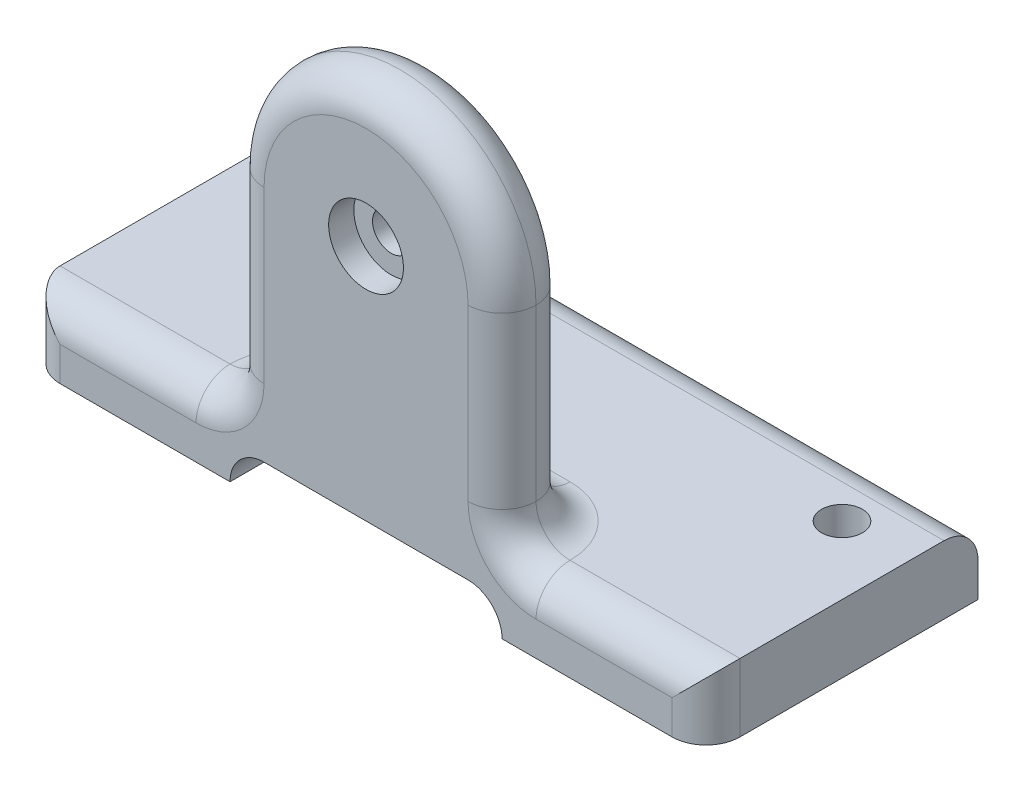
SolidWorks part; units mm, degrees
ref_plane "Plano frontal" through (0, 0, 0) normal (0, 0, 1) x (1, 0, 0)
ref_plane "Plano superior" through (0, 0, 0) normal (0, 1, 0) x (1, 0, 0)
ref_plane "Plano direito" through (0, 0, 0) normal (1, 0, 0) x (0, 0, -1)
sketch "Esboço1" plane through (0, 0, 0) normal (0, 1, 0) x (1, 0, 0)
  line L1 (-50, 20) -> (50, 20)
  line L2 (-50, 20) -> (-50, -20)
  line L3 (-50, -20) -> (50, -20)
  line L4 (50, 20) -> (50, -20)
  line L5 (-50, 20) -> (50, -20) construction
  line L6 (-50, -20) -> (50, 20) construction
  point P0 (0, 0)
  dimension "D1" = 100
  dimension "D2" = 40
extrude "Ressalto-extrusão1" add sketch "Esboço1" along normal blind 10
sketch "Esboço2" plane through (0, 0, 20) normal (0, 0, 1) x (1, 0, 0)
  line L0 (-20, 0) -> (-20, 40)
  line L1 (-50, 0) -> (50, 0) construction
  line L2 (20, 40) -> (20, 0)
  line L3 (20, 0) -> (-20, 0)
  arc A0 (-20, 40) -> (20, 40) centre (0, 40) cw
  dimension "D1" = 20
  dimension "D2" = 40
  dimension "D3" = 50
extrude "Ressalto-extrusão2" add sketch "Esboço2" against normal blind 10
sketch "Esboço3" plane through (0, 10, 0) normal (0, 1, 0) x (1, 0, 0)
  line L0 (50, 20) -> (-50, 20) construction
  line L1 (-50, 20) -> (-50, -20) construction
  line L2 (50, -20) -> (50, 20) construction
  circle A0 centre (-40, 10) radius 3
  circle A1 centre (40, 10) radius 3
  dimension "D4" = 6
  dimension "D5" = 6
  dimension "D1" = 10
  dimension "D2" = 10
  dimension "D3" = 10
extrude "Corte-extrusão1" cut sketch "Esboço3" against normal through all
sketch "Esboço4" plane through (0, 0, 20) normal (0, 0, 1) x (1, 0, 0)
  arc A0 (20, 40) -> (-20, 40) centre (0, 40) ccw construction
  point P0 (0, 40)
hole_wizard "Rebaixo para parafuso com cabeça panela de M51" positions "3DSketch1" profile "Esboço5" counterbore size "M5" standard "ISO" end condition up to next
sketch3d "3DSketch1"
  point P0 (0, 40, 20)
sketch "Esboço5" plane through (0, 40, 20) normal (1, 0, 0) x (0, -1, 0)
  line L0 (0, 0) -> (0, 10)
  line L1 (0, 10) -> (2.75, 10)
  line L3 (2.75, 10) -> (2.75, 3.7)
  line L4 (2.75, 3.7) -> (5.5, 3.7)
  line L5 (5.5, 3.7) -> (5.5, 0)
  line L7 (5.5, 0) -> (0, 0)
  line L11 (0, -6.35) -> (0, 107.95) construction
  dimension "Thru Hole Dia." = 5.5
  dimension "Thru Hole Depth" = 10
  dimension "C'Bore Dia." = 11
  dimension "C'Bore Depth" = 3.7
sketch "Esboço6" plane through (0, 0, 20) normal (0, 0, 1) x (1, 0, 0)
  line L0 (-20, 40) -> (-20, 10) construction
  line L1 (-20, 5) -> (20, 5)
  line L2 (-20, 5) -> (-20, 0)
  line L3 (-20, 0) -> (20, 0)
  line L4 (20, 5) -> (20, 0)
  line L5 (20, 10) -> (20, 40) construction
  line L6 (-50, 0) -> (50, 0) construction
  dimension "D1" = 5
extrude "Corte-extrusão2" cut sketch "Esboço6" against normal through all
fillet "Filete1" radius 5 14 edges at (-35, 10, 20) (0, 10, 10) (35, 10, 20) (-20, 25, 10) (0, 60, 10) (-20, 25, 20) (0, 60, 20) (20, 25, 10) (20, 25, 20) (0, 10, -20) (50, 5, 20) (-50, 5, 20) (20, 5, 0) (-20, 5, 0)
